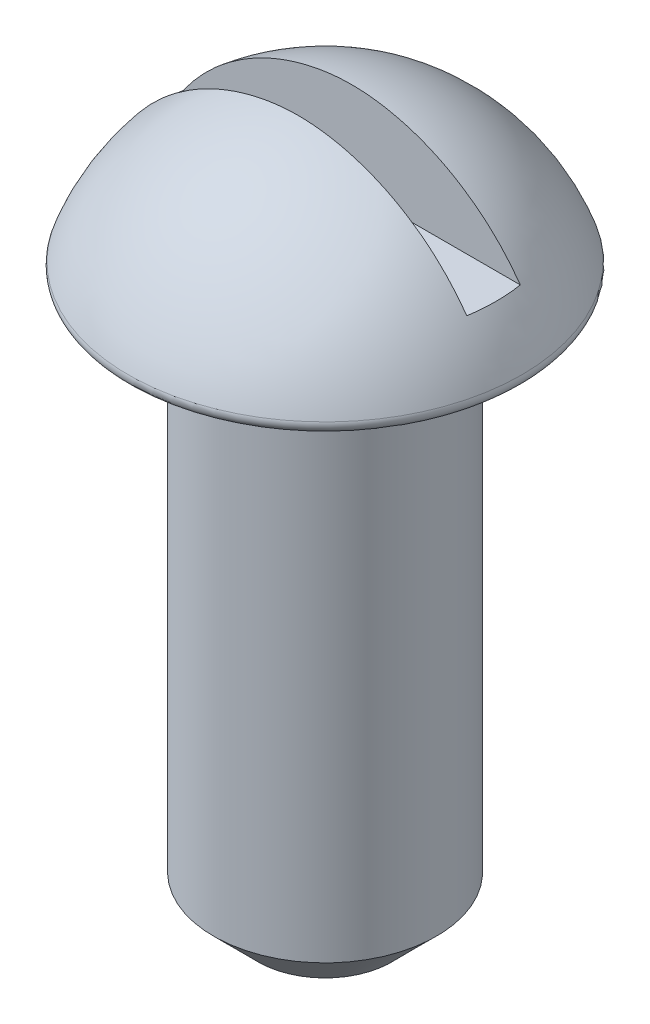
SolidWorks part; units mm, degrees
ref_plane "Спереди" through (0, 0, 0) normal (0, 0, 1) x (1, 0, 0)
ref_plane "Сверху" through (0, 0, 0) normal (0, 1, 0) x (1, 0, 0)
ref_plane "Справа" through (0, 0, 0) normal (1, 0, 0) x (0, 0, -1)
sketch "Эскиз1" plane through (0, 0, 0) normal (0, 0, 1) x (1, 0, 0)
  line L0 (0, 125.7632) -> (0, 0) construction
  line L1 (1.25, 90.535) -> (2.25, 90.535)
  line L2 (0, 92.235) -> (0, 84.2356)
  line L3 (0, 92.235) -> (0.3, 92.235)
  line L4 (1.25, 90.535) -> (1.25, 84.2356)
  line L6 (1.25, 84.2356) -> (0, 84.2356)
  arc A0 (0.3, 92.235) -> (2.25, 90.535) centre (-0.0535, 89.8612) cw
  dimension "D1" = 0.3
  dimension "D2" = 7.9994
  dimension "D3" = 1.7
  dimension "D4" = 2.25
  dimension "D6" = 2.4
  dimension "D5" = 1.25
revolve "Повернуть1" add sketch "Эскиз1" angle 360 about L0
ref_axis "Ось4" through (0, 0.28, 0) along (0, -1, 0)
sketch "Эскиз13" plane through (0, 92.235, 0) normal (0, 1, 0) x (-1, 0, 0)
  line L1 (2.25, -0.3) -> (-2.25, -0.3)
  line L2 (2.25, -0.3) -> (2.25, 0.3)
  line L3 (2.25, 0.3) -> (-2.25, 0.3)
  line L4 (-2.25, -0.3) -> (-2.25, 0.3)
  dimension "D1" = 2.25
  dimension "D2" = 4.5
  dimension "D3" = 0.3
  dimension "D4" = 0.6
extrude "Вырез-Вытянуть9" cut sketch "Эскиз13" against normal blind 1
fillet "Скругление1" radius 0.1 1 edges at (-2.25, 90.535, 0)
chamfer "Фаска1" distance 0.5 angle 45 1 edges at (-1.25, 84.2356, 0)
